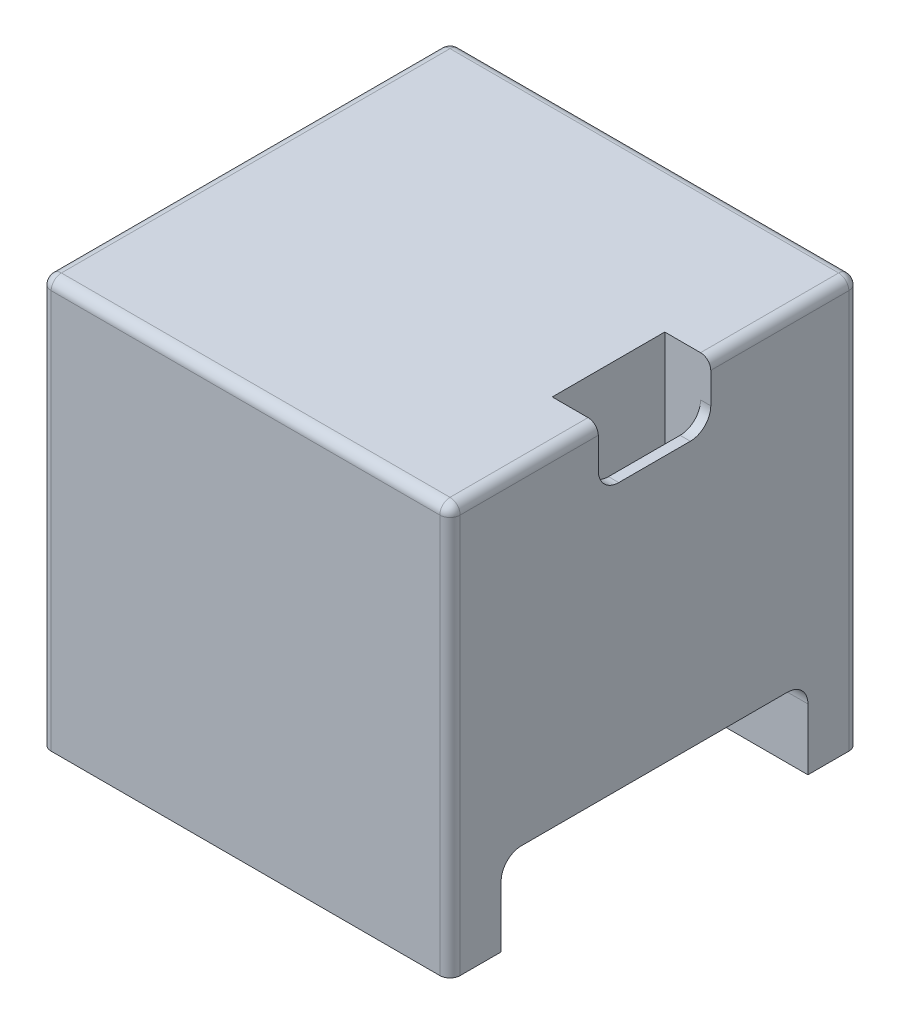
SolidWorks part; units mm, degrees
ref_plane "Front Plane" through (0, 0, 0) normal (0, 0, 1) x (1, 0, 0)
ref_plane "Top Plane" through (0, 0, 0) normal (0, 1, 0) x (1, 0, 0)
ref_plane "Right Plane" through (0, 0, 0) normal (1, 0, 0) x (0, 0, -1)
sketch "Sketch1" plane through (0, 0, 0) normal (0, 1, 0) x (1, 0, 0)
  line L1 (0, 0) -> (40, 0)
  line L2 (0, 0) -> (0, 40)
  line L3 (0, 40) -> (40, 40)
  line L4 (40, 0) -> (40, 40)
  dimension "D1" = 40
  dimension "D2" = 40
extrude "Boss-Extrude1" add sketch "Sketch1" along normal blind 40
sketch "Sketch2" plane through (0, 0, 0) normal (0, -1, 0) x (1, 0, 0)
  line L4 (0, 0) -> (0, -40)
  line L5 (0, -40) -> (40, -40)
  line L6 (40, -40) -> (40, 0)
  line L7 (40, 0) -> (0, 0)
  line L8 (0, -5) -> (0, -35)
  line L10 (40, -35) -> (40, -5)
  line L12 (0, -5) -> (40, -5)
  line L13 (0, -35) -> (40, -35)
  dimension "D2" = 5
  dimension "D4" = 5
  dimension "D7" = 5
  dimension "D8" = 5
  dimension "D1" = 0
extrude "Fork Cutout" cut sketch "Sketch2" against normal blind 8
sketch "Sketch5" plane through (0, 40, 0) normal (0, 1, 0) x (1, 0, 0)
  line L1 (39, 25.5) -> (35.5, 25.5)
  line L2 (39, 25.5) -> (39, 14.5)
  line L3 (39, 14.5) -> (35.5, 14.5)
  line L4 (35.5, 25.5) -> (35.5, 14.5)
  line L5 (0, 20) -> (40, 20) construction
  line L6 (0, 40) -> (0, 0) construction
  line L7 (40, 0) -> (40, 40) construction
  point P4 (39, 20)
  dimension "D1" = 11
  dimension "D2" = 3.5
  dimension "D3" = 1
extrude "Cut-Extrude3" cut sketch "Sketch5" against normal blind 25
fillet "Fillet5" radius 6 2 edges at (37.25, 15, -14.5) (37.25, 15, -25.5)
sketch "Sketch6" plane through (0, 40, 0) normal (0, 1, 0) x (1, 0, 0)
  line L1 (39, 14.5) -> (40, 14.5)
  line L2 (39, 14.5) -> (39, 25.5)
  line L3 (39, 25.5) -> (40, 25.5)
  line L4 (40, 14.5) -> (40, 25.5)
  line L5 (40, 0) -> (40, 40) construction
extrude "Cut-Extrude4" cut sketch "Sketch6" against normal blind 6
fillet "Fillet6" radius 2 2 edges at (39.5, 34, -25.5) (39.5, 34, -14.5)
fillet "Fillet8" radius 2 2 edges at (20, 8, -35) (20, 8, -5)
sketch "Sketch7" plane through (0, 0, 0) normal (-1, 0, 0) x (0, 0, 1)
  line L0 (-20, 40) -> (-20, 8) construction
  line L2 (-40, 40) -> (0, 40) construction
  line L3 (-7, 8) -> (-33, 8) construction
  line L4 (-5, 38.75) -> (-35, 38.75)
  line L5 (-5, 38.75) -> (-5, 8.75)
  line L6 (-5, 8.75) -> (-35, 8.75)
  line L7 (-35, 38.75) -> (-35, 8.75)
  dimension "D1" = 30
  dimension "D2" = 30
  dimension "D3" = 15
  dimension "D4" = 1.25
extrude "Boss-Extrude2" add sketch "Sketch7" along normal blind 0.1
sketch "Sketch11" plane through (-0.1, 0, 0) normal (-1, 0, 0) x (0, 0, 1)
  line L0 (-20, 38.75) -> (-20, 35) construction
  line L1 (-5, 38.75) -> (-35, 38.75) construction
  line L2 (-35, 8.75) -> (-5, 8.75) construction
  line L3 (-23.75, 12.5) -> (-31.25, 12.5)
  line L5 (-5, 23.75) -> (-35, 23.75) construction
  line L7 (-20, 23.75) -> (-31.25, 23.75)
  line L8 (-20, 23.75) -> (-20, 31.25)
  line L9 (-23.75, 35) -> (-31.25, 35)
  line L10 (-31.25, 23.75) -> (-31.25, 35)
  line L11 (-16.25, 35) -> (-8.75, 35)
  line L12 (-16.25, 35) -> (-16.25, 23.75)
  line L13 (-16.25, 23.75) -> (-12.5, 23.75)
  line L14 (-8.75, 35) -> (-8.75, 27.5)
  line L15 (-16.25, 20) -> (-31.25, 20)
  line L16 (-16.25, 20) -> (-16.25, 12.5)
  line L17 (-16.25, 12.5) -> (-20, 12.5)
  line L18 (-31.25, 20) -> (-31.25, 12.5)
  line L21 (-20, 31.25) -> (-23.75, 31.25)
  line L22 (-23.75, 35) -> (-23.75, 31.25)
  line L25 (-8.75, 27.5) -> (-12.5, 27.5)
  line L26 (-12.5, 23.75) -> (-12.5, 27.5)
  line L28 (-23.75, 12.5) -> (-23.75, 16.25)
  line L29 (-23.75, 16.25) -> (-20, 16.25)
  line L30 (-20, 12.5) -> (-20, 16.25)
  line L31 (-20, 31.25) -> (-20, 8.75) construction
  line L32 (-5, 8.75) -> (-5, 38.75) construction
  line L33 (-35, 38.75) -> (-35, 8.75) construction
  dimension "D1" = 11.25
  dimension "D2" = 11.25
  dimension "D3" = 3.75
  dimension "D4" = 3.75
  dimension "D5" = 3.75
  dimension "D6" = 3.75
  dimension "D7" = 3.75
  dimension "D8" = 3.75
  dimension "D9" = 7.5
  dimension "D10" = 11.25
  dimension "D11" = 7.5
  dimension "D12" = 3.75
  dimension "D13" = 3.75
  dimension "D14" = 7.5
  dimension "D15" = 3.75
extrude "Mark62" [suppressed] cut sketch "Sketch11" against normal blind 0.1
sketch "Sketch10" plane through (-0.1, 0, 0) normal (-1, 0, 0) x (0, 0, 1)
  line L0 (-20, 38.75) -> (-20, 8.75) construction
  line L1 (-20, 35) -> (-16.25, 35)
  line L2 (-20, 35) -> (-20, 31.25)
  line L3 (-20, 31.25) -> (-16.25, 31.25)
  line L4 (-16.25, 35) -> (-16.25, 31.25)
  line L5 (-20, 27.5) -> (-12.5, 27.5)
  line L6 (-20, 27.5) -> (-20, 16.25)
  line L7 (-20, 16.25) -> (-16.25, 16.25)
  line L8 (-12.5, 27.5) -> (-12.5, 20.1284)
  line L9 (-27.5, 35) -> (-23.75, 35)
  line L10 (-31.25, 30.9805) -> (-31.25, 12.5)
  line L11 (-31.25, 12.5) -> (-28.0767, 12.5)
  line L12 (-23.75, 35) -> (-23.75, 16.0712)
  line L13 (-5, 38.75) -> (-35, 38.75) construction
  line L15 (-35, 23.75) -> (-5, 23.75) construction
  line L17 (-5, 8.75) -> (-5, 38.75) construction
  line L18 (-35, 8.75) -> (-5, 8.75) construction
  line L21 (-23.75, 16.0712) -> (-28.0767, 16.0712)
  line L22 (-28.0767, 12.5) -> (-28.0767, 16.0712)
  line L25 (-31.25, 30.9805) -> (-27.5, 30.9805)
  line L26 (-27.5, 35) -> (-27.5, 30.9805)
  line L29 (-12.5, 20.1284) -> (-16.25, 20.1284)
  line L30 (-16.25, 16.25) -> (-16.25, 20.1284)
  line L31 (-35, 38.75) -> (-35, 8.75) construction
  dimension "D1" = 11.25
  dimension "D2" = 11.25
  dimension "D3" = 3.75
  dimension "D4" = 3.75
  dimension "D5" = 3.75
  dimension "D6" = 3.75
  dimension "D7" = 3.75
  dimension "D8" = 7.5
  dimension "D9" = 7.5
  dimension "D10" = 3.75
  dimension "D11" = 3.75
  dimension "D12" = 7.5
extrude "Mark38" cut sketch "Sketch10" against normal blind 0.1
fillet "Fillet9" radius 1 9 edges at (40, 20, 0) (40, 40, -7.25) (40, 40, -32.75) (40, 20, -40) (0, 20, -40) (0, 20, 0) (20, 40, 0) (0, 40, -20) (20, 40, -40)
